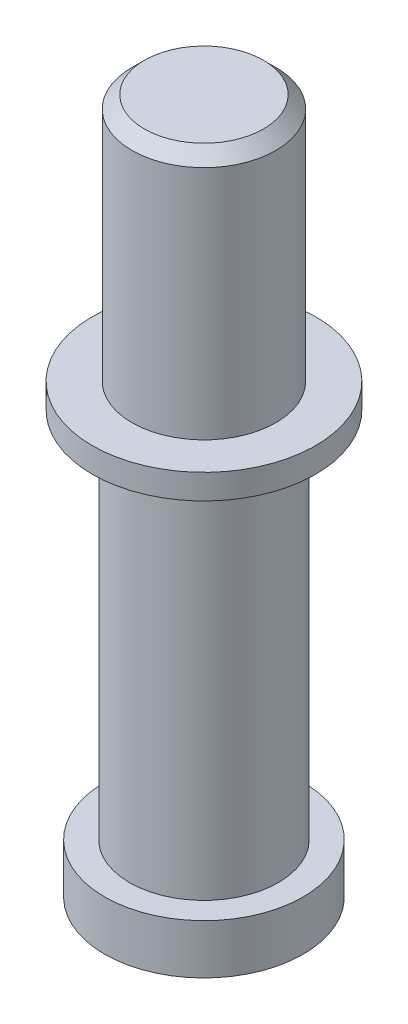
SolidWorks part; units mm, degrees
ref_plane "Front Plane" through (0, 0, 0) normal (0, 0, 1) x (1, 0, 0)
ref_plane "Top Plane" through (0, 0, 0) normal (0, 1, 0) x (1, 0, 0)
ref_plane "Right Plane" through (0, 0, 0) normal (1, 0, 0) x (0, 0, -1)
sketch "Sketch2" plane through (0, 0, 0) normal (0, 1, 0) x (1, 0, 0)
  circle A0 centre (0, 0) radius 2
  dimension "D1" = 4
extrude "Boss-Extrude1" add sketch "Sketch2" along normal blind 1
sketch "Sketch3" plane through (0, 1, 0) normal (0, 1, 0) x (1, 0, 0)
  circle A0 centre (0, 0) radius 1.5
extrude "Boss-Extrude2" add sketch "Sketch3" along normal blind 7.5
sketch "Sketch4" plane through (0, 8.5, 0) normal (0, 1, 0) x (1, 0, 0)
  circle A0 centre (0, 0) radius 2.25
  dimension "D1" = 4.5
extrude "Boss-Extrude3" add sketch "Sketch4" along normal blind 0.5
sketch "Sketch5" plane through (0, 9, 0) normal (0, 1, 0) x (1, 0, 0)
  circle A0 centre (0, 0) radius 1.45
  dimension "D1" = 2.9
extrude "Boss-Extrude4" add sketch "Sketch5" along normal blind 5
chamfer "Chamfer3" distance 0.25 angle 45 1 edges at (0, 14, 1.45)
